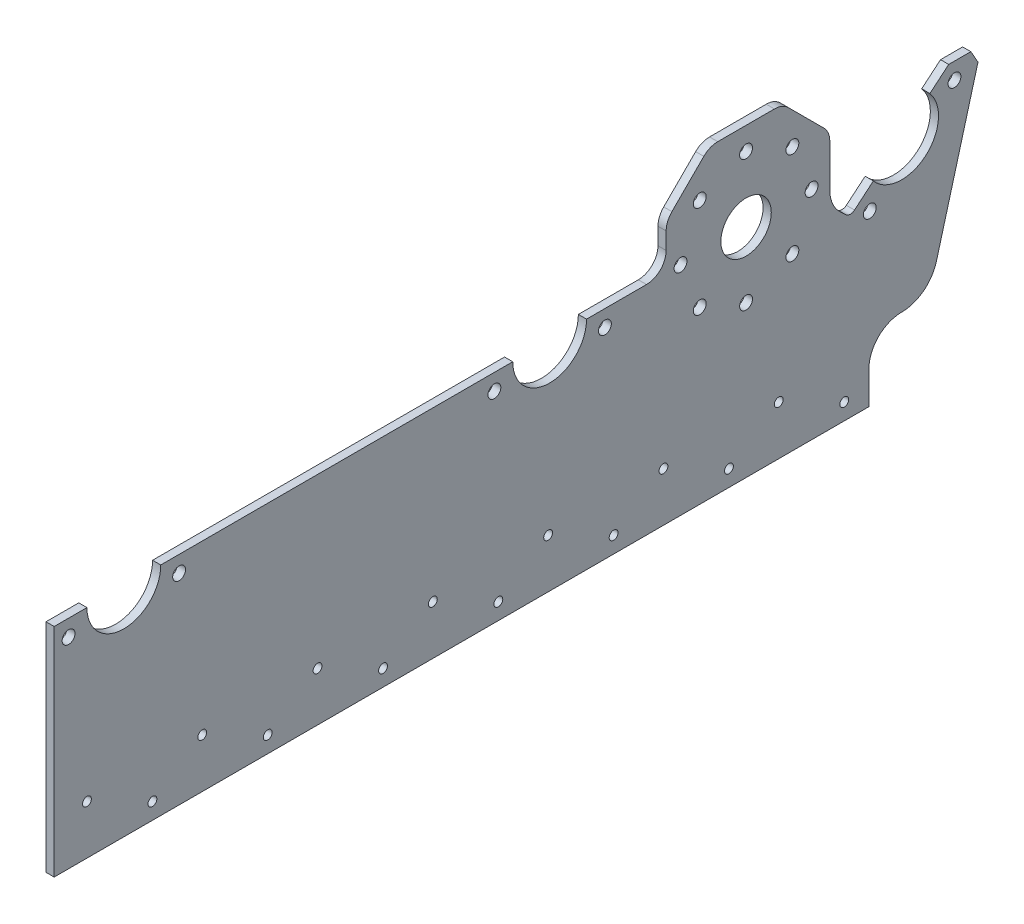
SolidWorks part; units mm, degrees
material "6061 Alloy"
ref_plane "Front Plane" through (0, 0, 0) normal (0, 0, 1) x (1, 0, 0)
ref_plane "Top Plane" through (0, 0, 0) normal (0, 1, 0) x (1, 0, 0)
ref_plane "Right Plane" through (0, 0, 0) normal (1, 0, 0) x (0, 0, -1)
sketch "Sketch1" plane through (0, 0, 0) normal (1, 0, 0) x (0, 0, -1)
  line L0 (-12.7, -12.7) -> (-328.6379, -12.7)
  line L1 (-328.6379, -12.7) -> (-328.6379, 71.4629)
  line L2 (-328.6379, 71.4629) -> (-315.9379, 71.4629)
  line L3 (-287.3121, 71.4629) -> (-150.8125, 71.4629)
  line L5 (10.9643, 80.6631) -> (18.2626, 86.7871)
  line L7 (-328.6379, 12.7) -> (13.4731, 12.7) construction
  line L8 (-12.7, -12.7) -> (-12.7, 0)
  line L9 (0, 12.4079) -> (0, 12.7) construction
  line L10 (13.4731, 22.9772) -> (30.9626, 86.7871)
  line L12 (-10.9643, 62.2627) -> (10.9643, 80.6631) construction
  line L13 (18.2626, 86.7871) -> (30.9626, 86.7871)
  line L14 (-122.1867, 71.4629) -> (-91.313, 71.4629)
  line L15 (-10.9643, 62.2627) -> (-18.2626, 56.1387)
  line L16 (-21.6532, 56.2511) -> (-23.945, 58.4485)
  line L18 (0, 71.4629) -> (-136.4996, 71.4629) construction
  line L19 (-328.6379, 15.875) -> (13.4731, 15.875) construction
  line L20 (-27.8553, 67.6154) -> (-27.8553, 87.307)
  line L21 (-27.8553, 87.307) -> (-46.1742, 105.6259)
  line L22 (-46.1742, 105.6259) -> (-74.4758, 105.6259)
  line L23 (-91.313, 88.7887) -> (-91.313, 71.4629)
  line L25 (-74.4758, 105.6259) -> (-91.313, 88.7887)
  arc A3 (0, 12.7) -> (13.4731, 22.9772) centre (0, 26.67) ccw
  arc A4 (0, 12.7) -> (-12.7, 0) centre (0, 0) ccw
  circle A5 centre (0, 0) radius 12.4079 construction
  arc A6 (-315.9379, 71.4629) -> (-287.3121, 71.4629) centre (-301.625, 71.4629) ccw
  arc A7 (-150.8125, 71.4629) -> (-122.1867, 71.4629) centre (-136.4996, 71.4629) ccw
  arc A8 (-10.9643, 62.2627) -> (10.9643, 80.6631) centre (0, 71.4629) ccw
  arc A9 (-18.2626, 56.1387) -> (-21.6532, 56.2511) centre (-19.8953, 58.0845) cw
  circle A11 centre (-60.325, 71.4629) radius 9.779
  arc A14 (-27.8553, 67.6154) -> (-23.945, 58.4485) centre (-15.1553, 67.6154) ccw
  circle A15 centre (-60.325, 71.4629) radius 25.4 construction
  circle A16 centre (-60.325, 96.8629) radius 2.413
  circle A17 centre (-42.3645, 89.4234) radius 2.413
  circle A18 centre (-34.925, 71.4629) radius 2.413
  circle A19 centre (-42.3645, 53.5024) radius 2.413
  circle A20 centre (-60.325, 46.0629) radius 2.413
  circle A21 centre (-78.2855, 53.5024) radius 2.413
  circle A22 centre (-85.725, 71.4629) radius 2.413
  circle A23 centre (-78.2855, 89.4234) radius 2.413
  point P4 (-170.669, -12.7)
  point P44 (-82.018, 71.4629)
  point P51 (-27.8553, 62.1979)
  point P60 (-60.325, 71.4629)
  dimension "D1" = 25.4
  dimension "D3" = 12.7
  dimension "D5" = 28.6258
  dimension "D6" = 3.175
  dimension "D7" = 13.97
  dimension "D8" = 12.7
  dimension "D10" = 24.8158
  dimension "D13" = 9.5273
  dimension "D14" = 140
  dimension "D15" = 2.54
  dimension "D16" = 50.8
  dimension "D17" = 60.325
  dimension "D18" = 41.275
  dimension "D24" = 3.175
  dimension "D26" = 12.7
  dimension "D19" = 4.826
  dimension "D25" = 6.35
  dimension "D29" = 6.35
  dimension "D20" = 4.6567
  dimension "D30" = 9.779
  dimension "D2" = 0
  dimension "D4" = 12.7
  dimension "D9" = 12.7
  dimension "D11" = 301.625
  dimension "D12" = 301.625
  dimension "D21" = 8
  dimension "D22" = 45
  dimension "D23" = 45
  dimension "D27" = 6.35
  dimension "D28" = 3.175
extrude "Boss-Extrude1" add sketch "Sketch1" along normal blind 3.175
hole_wizard "#10 Clearance Hole1" positions "Sketch2" profile "Sketch3" hole size "#10" standard "ANSI Inch" end condition through all
sketch "Sketch2" plane through (3.175, 0, 0) normal (1, 0, 0) x (0, 0, -1)
  line L0 (-323.0562, 65.1129) -> (-280.1937, 65.1129) construction
  line L2 (-157.9309, 65.1129) -> (-115.0683, 65.1129) construction
  line L4 (-12.3356, 52.8228) -> (20.499, 80.3743) construction
  line L6 (-315.9379, 71.4629) -> (-328.6379, 71.4629) construction
  line L7 (-301.625, 65.1129) -> (-301.625, 71.4629) construction
  line L9 (-136.4996, 71.4629) -> (-136.4996, 65.1129) construction
  line L11 (0, 71.4629) -> (4.0817, 66.5985) construction
  line L14 (18.2626, 86.7871) -> (10.9643, 80.6631) construction
  line L15 (18.2626, 86.7871) -> (10.9643, 80.6631) construction
  point P0 (-323.0562, 65.1129)
  point P2 (-280.1938, 65.1129)
  point P4 (-157.9309, 65.1129)
  point P6 (-115.0683, 65.1129)
  point P8 (-12.3356, 52.8228)
  point P10 (20.499, 80.3743)
  dimension "D1" = 42.8625
  dimension "D2" = 6.35
  dimension "D3" = 6.35
sketch "Sketch3" plane through (3.175, 65.1129, 323.0562) normal (0, 1, 0) x (0, 0, -1)
  line L0 (0, 0) -> (0, 3.175)
  line L1 (0, 3.175) -> (2.4892, 3.175)
  line L2 (2.4892, 3.175) -> (2.4892, 0)
  line L5 (2.4892, 0) -> (0, 0)
  line L11 (0, -6.35) -> (0, 107.95) construction
  dimension "Thru Hole Dia." = 4.9784
  dimension "Thru Hole Depth" = 3.175
hole_wizard "#10 Clearance Hole2" positions "Sketch5" profile "Sketch6" hole size "#10" standard "ANSI Inch"
sketch "Sketch5" plane through (3.175, 0, 0) normal (1, 0, 0) x (0, 0, -1)
  point P0 (-60.325, 96.8629)
  point P3 (-42.3645, 89.4234)
  point P6 (-34.925, 71.4629)
  point P9 (-42.3645, 53.5024)
  point P12 (-60.325, 46.0629)
  point P15 (-78.2855, 53.5024)
  point P18 (-85.725, 71.4629)
  point P21 (-78.2855, 89.4234)
sketch "Sketch6" plane through (3.175, 96.8629, 60.325) normal (0, 1, 0) x (0, 0, -1)
  line L0 (0, 0) -> (0, 4.6707)
  line L1 (0, 4.6707) -> (2.4892, 3.175)
  line L2 (2.4892, 3.175) -> (2.4892, 0)
  line L5 (2.4892, 0) -> (0, 0)
  line L10 (0, 4.6707) -> (-2.4892, 3.175) construction
  line L11 (0, -6.35) -> (0, 107.95) construction
  dimension "Hole Dia." = 4.9784
  dimension "Hole Depth" = 3.175
  dimension "Drill Angle" = 118
chamfer "Chamfer1" distance 5.08 angle 45 1 edges at (1.5875, 86.7871, -30.9626) first distance on face at (1.5875, 54.8821, -22.2179)
fillet "Fillet1" radius 7.62 5 edges at (1.5875, 87.307, 27.8553) (1.5875, 105.6259, 46.1742) (1.5875, 105.6259, 74.4758) (1.5875, 88.7887, 91.313) (1.5875, 71.4629, 91.313)
hole_wizard "1/8 (0.135) Diameter Hole1" positions "Sketch7" profile "Sketch8" hole size "1/8" standard "ANSI Inch"
sketch "Sketch7" plane through (0, 0, 0) normal (-1, 0, 0) x (0, 0, 1)
  line L0 (328.6379, -12.7) -> (12.7, -12.7) construction
  line L1 (12.7, -12.7) -> (12.7, 0) construction
  line L2 (328.6379, 71.4629) -> (328.6379, -12.7) construction
  point P0 (22.2504, -6.35)
  point P2 (47.6504, 6.35)
  point P19 (66.965, -6.35)
  point P20 (92.365, 6.35)
  point P21 (111.6796, -6.35)
  point P22 (137.0796, 6.35)
  point P23 (156.3941, -6.35)
  point P24 (181.7941, 6.35)
  point P25 (201.1087, -6.35)
  point P26 (226.5087, 6.35)
  point P27 (245.8233, -6.35)
  point P28 (271.2233, 6.35)
  point P29 (290.5379, -6.35)
  point P30 (315.9379, 6.35)
  dimension "D1" = 6.35
  dimension "D2" = 25.4
  dimension "D3" = 12.7
  dimension "D4" = 9.5504
  dimension "D6" = 12.7
  dimension "D5" = 7
sketch "Sketch8" plane through (0, -6.35, 22.2504) normal (0, 1, 0) x (0, 0, 1)
  line L0 (0, 0) -> (0, 17.5402)
  line L1 (0, 17.5402) -> (1.7145, 16.51)
  line L2 (1.7145, 16.51) -> (1.7145, 0)
  line L5 (1.7145, 0) -> (0, 0)
  line L10 (0, 17.5402) -> (-1.7145, 16.51) construction
  line L11 (0, -6.35) -> (0, 107.95) construction
  dimension "Hole Dia." = 3.429
  dimension "Hole Depth" = 16.51
  dimension "Drill Angle" = 118
